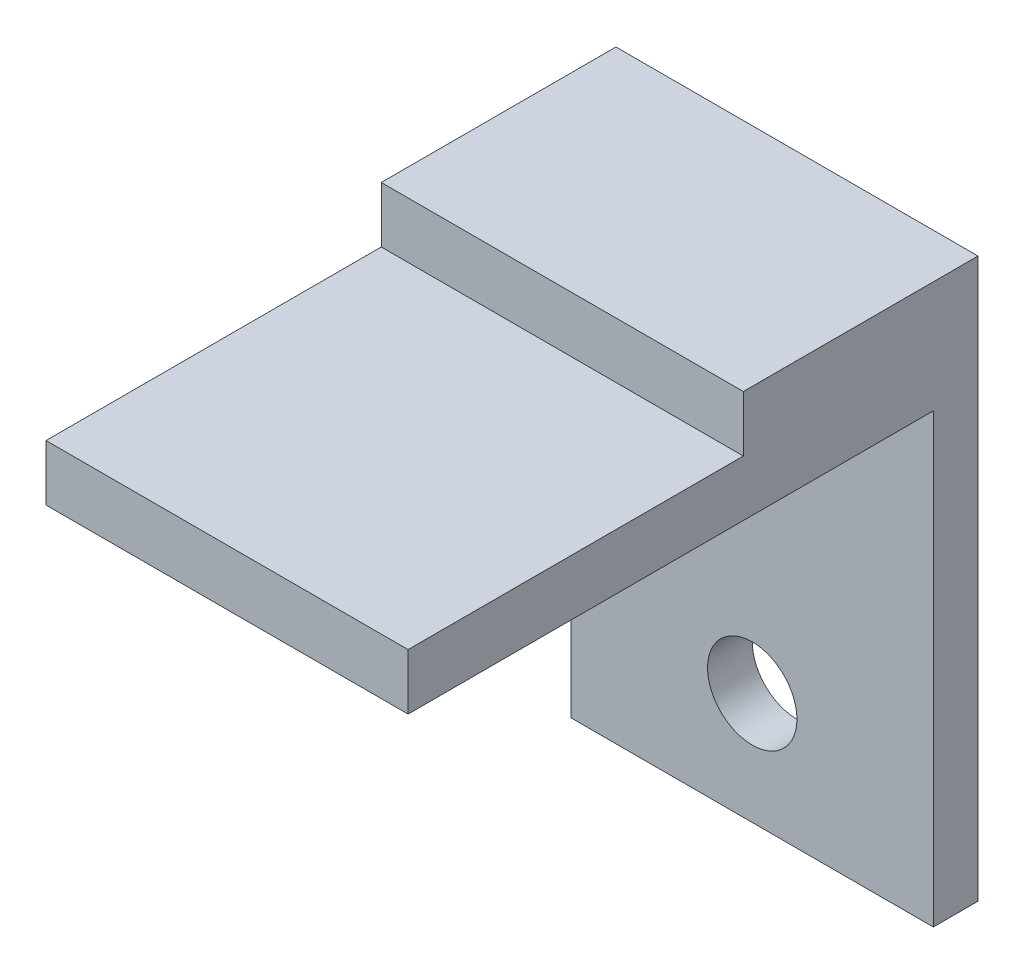
SolidWorks part; units mm, degrees
note: The reader was unsure of these and kept them because the rebuilt part matched: shared geometry of "Sketch1<3>", "Sketch1<4>", "Sketch1<8>", "Sketch1<9>", "Sketch1<11>", "Sketch1<12>".
ref_plane "Front Plane" through (0, 0, 0) normal (0, 0, 1) x (1, 0, 0)
ref_plane "Top Plane" through (0, 0, 0) normal (0, 1, 0) x (1, 0, 0)
ref_plane "Right Plane" through (0, 0, 0) normal (1, 0, 0) x (0, 0, -1)
sketch "Sketch1" plane through (0, 0, 0) normal (0, 0, 1) x (1, 0, 0)
  line L0 (0, 62.1454) -> (0, -46.6941) construction
  line L1 (-111.1538, 0) -> (74.1933, 0) construction
  line L3 (-8.1, 12.5) -> (8.1, 12.5)
  line L4 (-8.1, 12.5) -> (-8.1, -12.5)
  line L5 (-8.1, -12.5) -> (8.1, -12.5)
  line L6 (8.1, 12.5) -> (8.1, -12.5)
  line L7 (-1, -0.5) -> (1, -0.5)
  line L8 (-1, -0.5) -> (-1, -2.5)
  line L9 (-1, -2.5) -> (1, -2.5)
  line L10 (1, -0.5) -> (1, -2.5)
  line L11 (-8.1, 12.5) -> (-5.1, 12.5)
  line L12 (-8.1, 12.5) -> (-8.1, 3.5)
  line L13 (-8.1, 3.5) -> (-5.1, 3.5)
  line L14 (-5.1, 12.5) -> (-5.1, 3.5)
  line L15 (-8.1, 12.5) -> (8.1, 12.5)
  line L16 (-8.1, 12.5) -> (-8.1, 3.5)
  line L17 (-8.1, 3.5) -> (8.1, 3.5)
  line L18 (8.1, 12.5) -> (8.1, 3.5)
  line L19 (8.1, 12.5) -> (-8.1, 12.5)
  line L20 (8.1, 12.5) -> (8.1, 7.5)
  line L21 (8.1, 7.5) -> (-8.1, 7.5)
  line L22 (-8.1, 12.5) -> (-8.1, 7.5)
  line L23 (8.1, 7.5) -> (-8.1, 7.5)
  line L24 (8.1, 7.5) -> (8.1, 10)
  line L25 (8.1, 10) -> (-8.1, 10)
  line L26 (-8.1, 7.5) -> (-8.1, 10)
  circle A0 centre (0, -7.5) radius 2
  dimension "D3" = 4
  dimension "D4" = 3
  dimension "D1" = 16.2
  dimension "D2" = 25
  dimension "D5" = 2
  dimension "D6" = 2
  dimension "D7" = 3
  dimension "D8" = 9
  dimension "D9" = 3
  dimension "D10" = 5
  dimension "D11" = 2.5
extrude "Boss-Extrude3" add sketch "Sketch1" along normal blind 2 contours L3 L14 L13 L4 L5 L6 A0 L7 L10 L9 L8 | L10 L7 L8 L9
extrude "Boss-Extrude4" add sketch "Sketch1<3>" along normal blind 25.5 contours L14 L3 L4 L13
sketch "Sketch1<3>" plane through (0, 0, 0) normal (0, 0, 1) x (1, 0, 0) same geometry as "Sketch1"
extrude "Boss-Extrude5" add sketch "Sketch1<4>" against normal blind 1.5 contours L10 L7 L8 L9
sketch "Sketch1<4>" plane through (0, 0, 0) normal (0, 0, 1) x (1, 0, 0) same geometry as "Sketch1"
extrude "Boss-Extrude6" add sketch "Sketch1<8>" along normal blind 2 contours L14 L17 L6 L3
sketch "Sketch1<8>" plane through (0, 0, 0) normal (0, 0, 1) x (1, 0, 0) same geometry as "Sketch1"
extrude "Boss-Extrude7" add sketch "Sketch1<9>" along normal blind 2 contours L18 L21 L14 L17 | L14 L21 L16 L13
sketch "Sketch1<9>" plane through (0, 0, 0) normal (0, 0, 1) x (1, 0, 0) same geometry as "Sketch1"
extrude "Boss-Extrude9" add sketch "Sketch1<11>" along normal blind 10.5 contours L25 L14 L3 L4 | L25 L6 L3 L14
sketch "Sketch1<11>" plane through (0, 0, 0) normal (0, 0, 1) x (1, 0, 0) same geometry as "Sketch1"
extrude "Boss-Extrude10" add sketch "Sketch1<12>" along normal blind 25.5 contours L20 L25 L14 L21
sketch "Sketch1<12>" plane through (0, 0, 0) normal (0, 0, 1) x (1, 0, 0) same geometry as "Sketch1"
